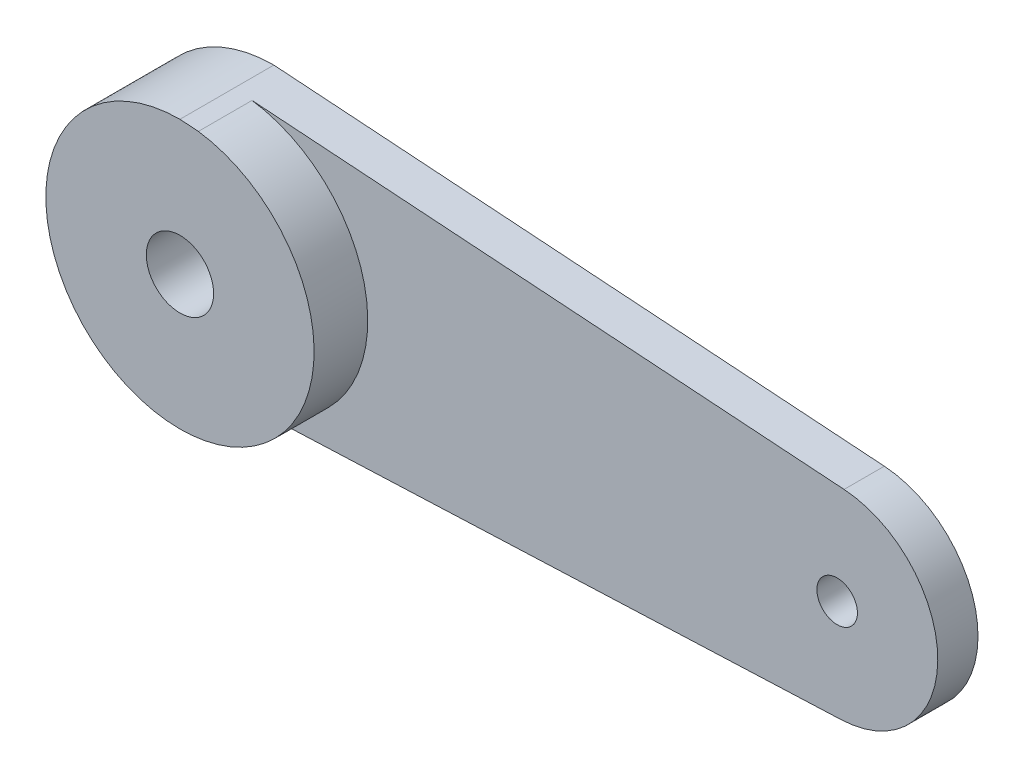
SolidWorks part; units mm, degrees
ref_plane "Front Plane" through (0, 0, 0) normal (0, 0, 1) x (1, 0, 0)
ref_plane "Top Plane" through (0, 0, 0) normal (0, 1, 0) x (1, 0, 0)
ref_plane "Right Plane" through (0, 0, 0) normal (1, 0, 0) x (0, 0, -1)
sketch "Sketch1" plane through (0, 0, 0) normal (0, 0, 1) x (1, 0, 0)
  line L0 (0, 10) -> (45.5121, 6.8586)
  line L1 (0, -10) -> (45.3071, -8.1171)
  circle A0 centre (0, 0) radius 10
  circle A1 centre (44.9957, -0.6236) radius 7.5
  circle A2 centre (0, 0) radius 2.51
  circle A3 centre (44.9957, -0.6236) radius 1.51
  dimension "D2" = 20
  dimension "D3" = 15
  dimension "D4" = 5.02
  dimension "D5" = 3.02
  dimension "D1" = 45
extrude "Boss-Extrude1" add sketch "Sketch1" along normal blind 7 contours L0 A0 L1 A2 region at (0.6675, 9.6704, 0)
extrude "Boss-Extrude2" add sketch "Sketch1<3>" along normal blind 3 contours A1 L0 A0 L1 | A1 A3 region at (23.0889, -0.3255, 0) region at (50.3235, 4.3492, 0)
sketch "Sketch1<3>" plane through (0, 0, 0) normal (0, 0, 1) x (1, 0, 0) same geometry as "Sketch1"
